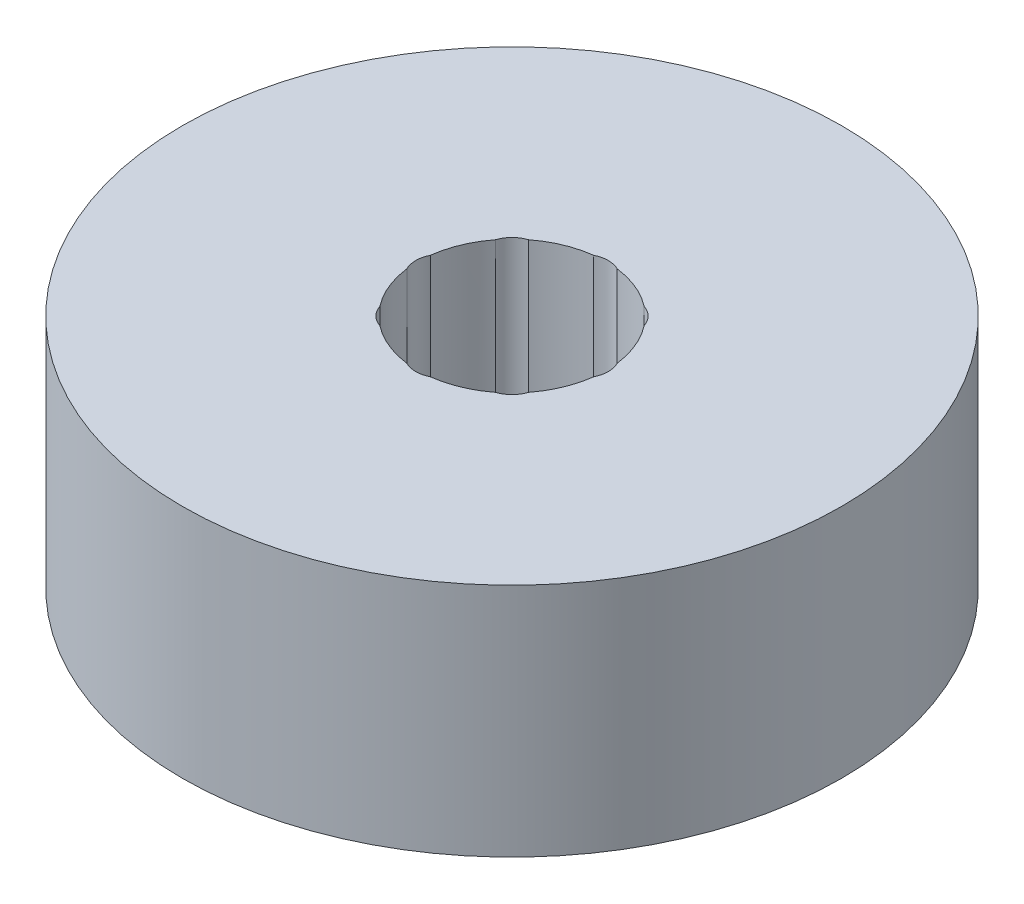
SolidWorks part; units mm, degrees
ref_plane "Front Plane" through (0, 0, 0) normal (0, 0, 1) x (1, 0, 0)
ref_plane "Top Plane" through (0, 0, 0) normal (0, 1, 0) x (1, 0, 0)
ref_plane "Right Plane" through (0, 0, 0) normal (1, 0, 0) x (0, 0, -1)
sketch "Sketch1" plane through (0, 0, 0) normal (0, 1, 0) x (1, 0, 0)
  circle A0 centre (0, 0) radius 35
  dimension "FLANGE_OD" = 70
extrude "Boss-Extrude1" add sketch "Sketch1" along normal blind 25
sketch "Sketch2" plane through (0, 0, 0) normal (0, 1, 0) x (1, 0, 0)
  circle A0 centre (0, 0) radius 10
  dimension "BORE_D" = 20
extrude "Cut-Extrude1" cut sketch "Sketch2" along normal through all
sketch "Sketch3" plane through (0, 25, 0) normal (0, 1, 0) x (1, 0, 0)
  circle A0 centre (0, 0) radius 7.4405 construction
  circle A1 centre (-7.4405, 0) radius 2.7774
  dimension "BOLT_D" = 5.5548
  dimension "BOLT_PCD" = 14.881
extrude "Cut-Extrude2" cut sketch "Sketch3" against normal blind 18.3636
pattern_circular "CirPattern1" count 8 over 360 about axis through (0, 0, 0) along (0, 1, 0) of "Cut-Extrude2"
